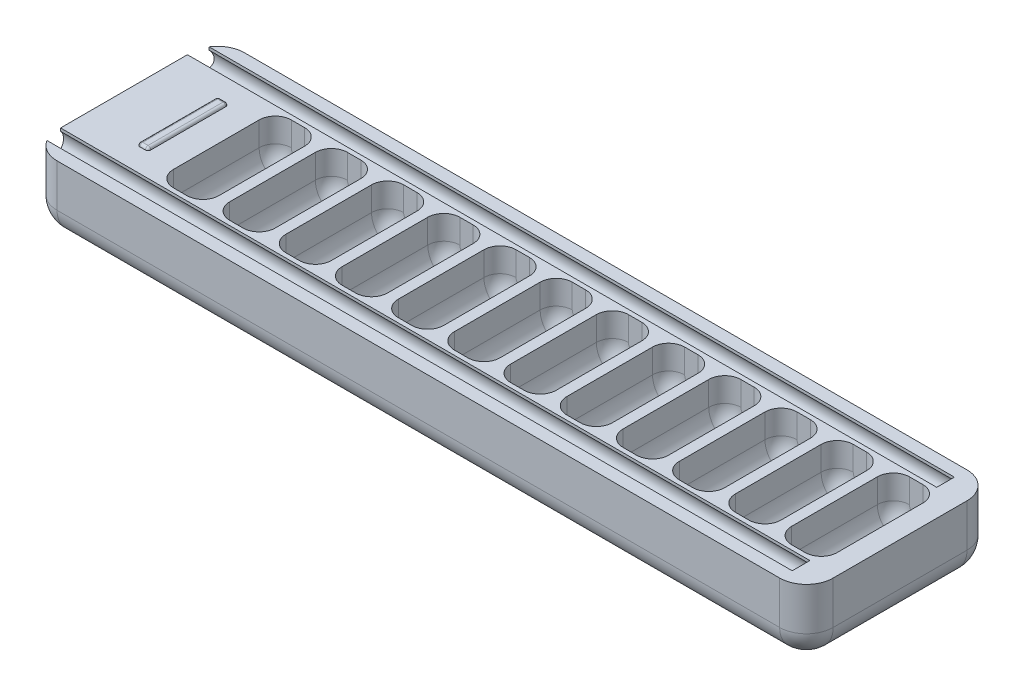
SolidWorks part; units mm, degrees
ref_plane "前视基准面" through (0, 0, 0) normal (0, 0, 1) x (1, 0, 0)
ref_plane "上视基准面" through (0, 0, 0) normal (0, 1, 0) x (1, 0, 0)
ref_plane "右视基准面" through (0, 0, 0) normal (1, 0, 0) x (0, 0, -1)
sketch "草图1" plane through (0, 0, 0) normal (0, 1, 0) x (1, 0, 0)
  line L1 (-72.5, 17.5) -> (72.5, 17.5)
  line L2 (-72.5, 17.5) -> (-72.5, -17.5)
  line L3 (-72.5, -17.5) -> (72.5, -17.5)
  line L4 (72.5, 17.5) -> (72.5, -17.5)
  line L5 (-72.5, 17.5) -> (72.5, -17.5) construction
  line L6 (-72.5, -17.5) -> (72.5, 17.5) construction
  point P0 (0, 0)
  dimension "D1" = 35
  dimension "D2" = 145
extrude "凸台-拉伸1" add sketch "草图1" along normal blind 13
fillet "圆角1" radius 5 4 edges at (-72.5, 0, 0) (72.5, 0, 0) (0, 0, -17.5) (0, 0, 17.5)
fillet "圆角2" radius 5 8 edges at (71.0355, 1.4645, 16.0355) (71.0355, 1.4645, -16.0355) (-71.0355, 1.4645, -16.0355) (-71.0355, 1.4645, 16.0355) (72.5, 9, 17.5) (72.5, 9, -17.5) (-72.5, 9, -17.5) (-72.5, 9, 17.5)
sketch "草图2" plane through (0, 0, 0) normal (0, 0, 1) x (1, 0, 0)
  line L2 (-55.25, 8.5) -> (-55.25, 13)
  line L3 (-55.25, 13) -> (-46.75, 13)
  line L4 (-46.75, 13) -> (-46.75, 8.5)
  line L5 (-67.5, 13) -> (67.5, 13) construction
  circle A0 centre (-51, 8.5) radius 4.25
  dimension "D1" = 8.5
  dimension "D2" = 51
  dimension "D3" = 8.5
extrude "切除-拉伸1" cut sketch "草图2" against normal blind 11 and the other way blind 11 contours A0 L3 L2 | A0 | A0 L4 L3
pattern_linear "阵列(线性)1" count 12 spacing 10.5 along (1, 0, 0) of "切除-拉伸1"
sketch "草图3" plane through (-72.5, 0, 0) normal (-1, 0, 0) x (0, 0, 1)
  line L0 (-13.5, 11) -> (13.5, 11) construction
  line L1 (17.5, 13) -> (17.5, 5) construction
  line L2 (0, 0) -> (0, 11) construction
  line L4 (-15.15, 15.4) -> (-11.85, 15.4)
  line L5 (-15.15, 15.4) -> (-15.15, 11)
  line L6 (-15.15, 11) -> (-11.85, 11)
  line L7 (-11.85, 15.4) -> (-11.85, 11)
  line L8 (-15.15, 15.4) -> (-11.85, 11) construction
  line L9 (-15.15, 11) -> (-11.85, 15.4) construction
  line L10 (11.85, 15.4) -> (15.15, 15.4)
  line L11 (11.85, 15.4) -> (11.85, 11)
  line L12 (11.85, 11) -> (15.15, 11)
  line L13 (15.15, 15.4) -> (15.15, 11)
  line L14 (11.85, 15.4) -> (15.15, 11) construction
  line L15 (11.85, 11) -> (15.15, 15.4) construction
  circle A0 centre (-13.5, 11) radius 2.2
  circle A1 centre (13.5, 11) radius 2.2
  point P4 (13.5, 13.2)
  point P10 (-13.5, 13.2)
  line M2 (12.5, 13) -> (-12.5, 13)
  line M9 (12.5, 5) -> (12.5, 13)
  line M11 (-12.5, 13) -> (-12.5, 5)
  dimension "D1" = 4.4
  dimension "D2" = 4
  dimension "D3" = 11
  dimension "D4" = 3.3
  dimension "D5" = 3.3
extrude "切除-拉伸2" cut sketch "草图3" against normal blind 140 contours A1 L13 L12 M9 | A1 M9 | L13 A1 L12 M9 | L7 A0 L5 L6 | L5 A0 L6 M11 | A0 L7 M11 | A0 L7 L4 L5 M11 | A1 L13 L10 L11 | L7 A0 L6 M11 | A0 L7 M2 M11 | A1 L11 L12 M9 | A1 L11 M9 M2
fillet "圆角3" radius 3 54 edges at (7.75, 10.75, 11) (7.75, 10.75, -11) (16.25, 10.75, 11) (16.25, 10.75, -11) (-2.75, 10.75, 11) (-2.75, 10.75, -11) (1.5, 4.25, 11) (1.5, 4.25, -11) (-13.25, 10.75, 11) (-13.25, 10.75, -11) (-9, 4.25, 11) (-9, 4.25, -11) (-23.75, 10.75, 11) (-23.75, 10.75, -11) (-19.5, 4.25, 11) (-19.5, 4.25, -11) (-34.25, 10.75, 11) (-34.25, 10.75, -11) (-30, 4.25, 11) (-30, 4.25, -11) (-44.75, 10.75, 11) (-44.75, 10.75, -11) (-40.5, 4.25, 11) (-40.5, 4.25, -11) (-55.25, 10.75, 11) (-55.25, 10.75, -11) (-51, 4.25, 11) (-51, 4.25, -11) (12, 4.25, 11) (12, 4.25, -11) (18.25, 10.75, 11) (18.25, 10.75, -11) (22.5, 4.25, 11) (22.5, 4.25, -11) (28.75, 10.75, 11) (28.75, 10.75, -11) (33, 4.25, 11) (33, 4.25, -11) (5.75, 10.75, 11) (5.75, 10.75, -11) (-4.75, 10.75, 11) (-4.75, 10.75, -11) (-15.25, 10.75, 11) (-15.25, 10.75, -11) (-25.75, 10.75, 11) (-25.75, 10.75, -11) (-36.25, 10.75, 11) (-36.25, 10.75, -11) (-46.75, 10.75, 11) (-46.75, 10.75, -11) (26.75, 10.75, 11) (26.75, 10.75, -11) (37.25, 10.75, 11) (37.25, 10.75, -11)
fillet "圆角4" radius 3 18 edges at (39.25, 10.75, 11) (39.25, 10.75, -11) (47.75, 10.75, 11) (47.75, 10.75, -11) (49.75, 10.75, 11) (49.75, 10.75, -11) (58.25, 10.75, 11) (58.25, 10.75, -11) (60.25, 10.75, 11) (60.25, 10.75, -11) (68.75, 10.75, 11) (68.75, 10.75, -11) (43.5, 4.25, 11) (43.5, 4.25, -11) (54, 4.25, 11) (54, 4.25, -11) (64.5, 4.25, 11) (64.5, 4.25, -11)
sketch "草图4" plane through (0, 13, 0) normal (0, 1, 0) x (1, 0, 0)
  line L0 (-72.5, 0) -> (-62.5, 0) construction
  line L1 (-62.5, 7.5) -> (-60.5, 7.5)
  line L2 (-62.5, 7.5) -> (-62.5, -7.5)
  line L3 (-62.5, -7.5) -> (-60.5, -7.5)
  line L4 (-60.5, 7.5) -> (-60.5, -7.5)
  line L5 (-72.5, 11.85) -> (-72.5, -11.85) construction
  dimension "D1" = 2
  dimension "D2" = 10
  dimension "D3" = 15
extrude "凸台-拉伸2" add sketch "草图4" along normal blind 0.5
fillet "圆角5" radius 0.5 4 edges at (-60.5, 13.5, 0) (-62.5, 13.5, 0) (-61.5, 13.5, -7.5) (-61.5, 13.5, 7.5)
